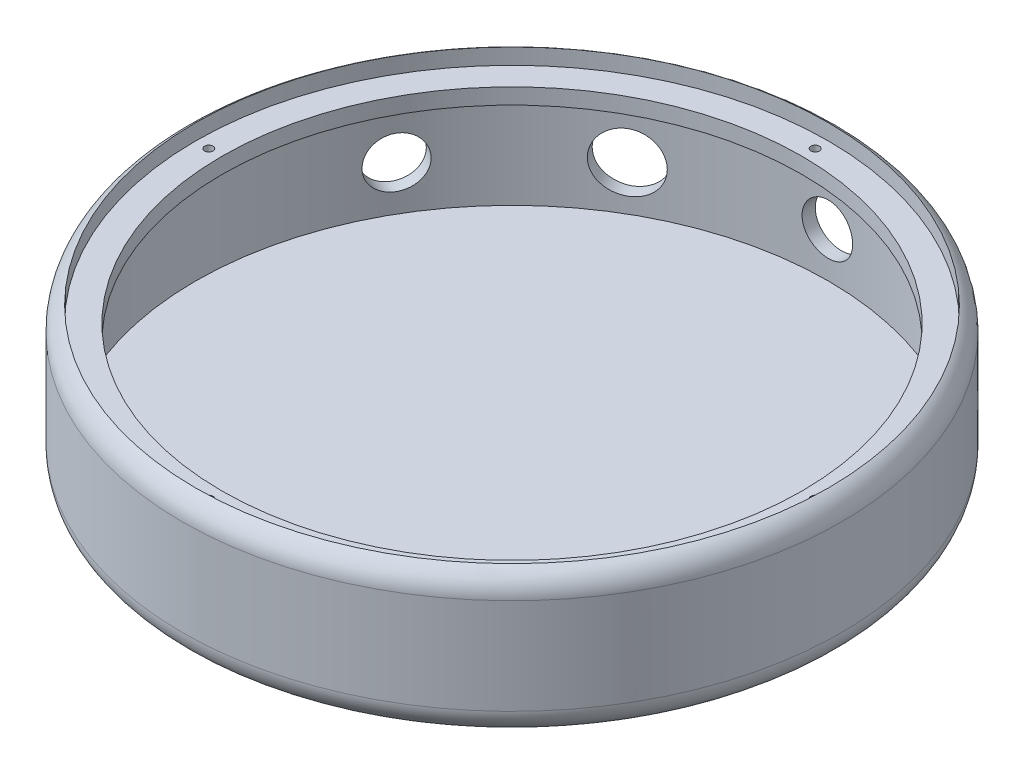
SolidWorks part; units mm, degrees
ref_plane "前视基准面" through (0, 0, 0) normal (0, 0, 1) x (1, 0, 0)
ref_plane "上视基准面" through (0, 0, 0) normal (0, 1, 0) x (1, 0, 0)
ref_plane "右视基准面" through (0, 0, 0) normal (1, 0, 0) x (0, 0, -1)
other "Configuration Table"
sketch "草图21" plane through (0, 0, 0) normal (0, 1, 0) x (1, 0, 0)
  circle A0 centre (0, 0) radius 125
  dimension "D1" = 250
extrude "凸台-拉伸1" add sketch "草图21" along normal blind 55 contours A0
sketch "草图22" plane through (0, 55, 0) normal (0, 1, 0) x (1, 0, 0)
  circle A0 centre (0, 0) radius 120
  dimension "D1" = 240
extrude "切除-拉伸1" cut sketch "草图22" against normal blind 52
sketch "草图23" plane through (0, 55, 0) normal (0, 1, 0) x (1, 0, 0)
  circle A0 centre (0, 0) radius 120
  circle A1 centre (0, 0) radius 110
  dimension "D1" = 220
  dimension "D2" = 240
extrude "凸台-拉伸2" add sketch "草图23" against normal blind 12
sketch "草图24" plane through (0, 55, 0) normal (0, 1, 0) x (1, 0, 0)
  circle A0 centre (0, 0) radius 110
  circle A1 centre (0, 0) radius 120
  dimension "D1" = 220
  dimension "D2" = 240
extrude "切除-拉伸2" cut sketch "草图24" against normal blind 6
sketch "草图25" plane through (0, 49, 0) normal (0, 1, 0) x (1, 0, 0)
  line L0 (0, 115) -> (0, 0)
  line L1 (-115, 0) -> (0, 0)
  circle A0 centre (0, 115) radius 1.6
  circle A1 centre (115, 0) radius 1.6
  circle A2 centre (0, -115) radius 1.6
  circle A3 centre (-115, 0) radius 1.6
  point P13 (0, 0)
  dimension "D1" = 3.2
  dimension "D2" = 115
  dimension "D4" = 115
  dimension "D3" = 4
extrude "切除-拉伸3" cut sketch "草图25" against normal blind 10 contours A3 | A0 | A1 | A2
fillet "圆角1" radius 10 1 edges at (0, 0, 125)
fillet "圆角2" radius 10 1 edges at (0, 55, 125)
sketch "草图26" plane through (0, 0, 0) normal (0, 0, 1) x (1, 0, 0)
  line L0 (0, 0) -> (0, 20)
  line L1 (-115, 0) -> (115, 0) construction
  circle A0 centre (0, 20) radius 9.6
  dimension "D1" = 19.2
  dimension "D2" = 20
extrude "切除-拉伸4" cut sketch "草图26" against normal blind 1202 contours A0
sketch "草图27" plane through (0, 0, 0) normal (0, 0, 1) x (1, 0, 0)
  line L0 (0, 0) -> (0, 31.8663)
  dimension "D1" = 31.8663
ref_plane "基准面2" through (0, 0, 0) normal (0.5, 0, 0.866) x (0, 1, 0)
sketch "草图28" plane through (0, 0, 0) normal (0.5, 0, 0.866) x (0, 1, 0)
  line L1 (0, 0) -> (31.8663, 0) construction
  circle A0 centre (20, 0) radius 11.1
  dimension "D2" = 22.2
  dimension "D1" = 20
extrude "切除-拉伸5" cut sketch "草图28" against normal blind 1202
ref_plane "基准面3" through (0, 0, 0) normal (-0.5, 0, 0.866) x (0, 1, 0)
sketch "草图30" plane through (0, 0, 0) normal (-0.5, 0, 0.866) x (0, 1, 0)
  line L0 (0, 0) -> (31.8663, 0) construction
  circle A0 centre (15, 0) radius 6.025
  dimension "D1" = 15
  dimension "D2" = 12.05
extrude "切除-拉伸6" cut sketch "草图30" against normal blind 1202
ref_plane "基准面4" through (0, 0, 0) normal (0.866, 0, 0.5) x (0, 1, 0)
sketch "草图31" plane through (0, 0, 0) normal (0.866, 0, 0.5) x (0, 1, 0)
  line L0 (0, 0) -> (31.8663, 0) construction
  circle A0 centre (20, 0) radius 9.6
  dimension "D1" = 19.2
  dimension "D2" = 20
extrude "切除-拉伸7" cut sketch "草图31" against normal blind 1000
